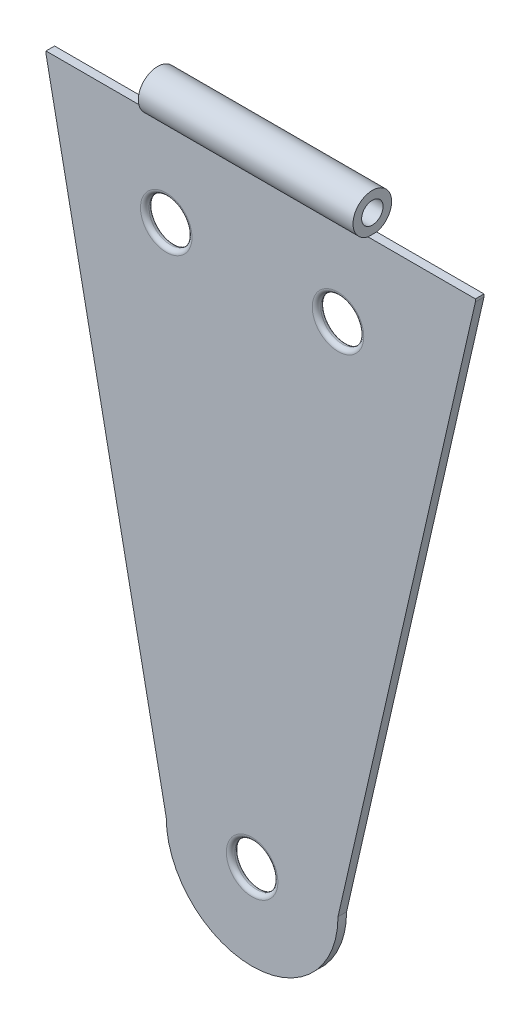
SolidWorks part; units mm, degrees
material "Liga de aço fundido"
ref_plane "Plano frontal" through (0, 0, 0) normal (0, 0, 1) x (1, 0, 0)
ref_plane "Plano superior" through (0, 0, 0) normal (0, 1, 0) x (1, 0, 0)
ref_plane "Plano direito" through (0, 0, 0) normal (1, 0, 0) x (0, 0, -1)
sketch "Esboço1" plane through (0, 0, 0) normal (0, 0, 1) x (1, 0, 0)
  line L5 (-50, 0) -> (50, 0)
  line L6 (-50, 0) -> (-22, 0) construction
  line L17 (-22, 0) -> (-22, -20) construction
  line L31 (-50, 0) -> (-22, -140)
  line L33 (18, -140) -> (50, 0)
  arc A7 (-22, -140) -> (18, -140) centre (-2, -140) ccw
  circle A8 centre (-2, -140) radius 5
  circle A9 centre (-22, -20) radius 5
  circle A10 centre (18, -20) radius 5
  point P5 (0, 0)
  point P10 (0, 0)
  point P12 (0, 0)
  point P13 (0, 0)
  dimension "D3" = 10
  dimension "D6" = 10
  dimension "D1" = 40
  dimension "D2" = 100
  dimension "D4" = 140
  dimension "D5" = 281.31
  dimension "D7" = 20
extrude "Ressalto-extrusão1" add sketch "Esboço1" along normal blind 2 contours A7 L33 L5 L31 | A9 | A10 | A8
fillet "Filete1" radius 1 6 edges at (3, -140, 2) (3, -140, 0) (23, -20, 2) (23, -20, 0) (-17, -20, 2) (-17, -20, 0)
sketch "Esboço6" plane through (0, 0, 0) normal (0, 1, 0) x (1, 0, 0)
  line L4 (50, 0) -> (-50, 0)
  line L5 (-50, 0) -> (-50, -2)
  line L6 (50, 0) -> (-50, 0)
  line L7 (50, -2) -> (50, 0)
  line L9 (-50, 0) -> (-50, -2)
  line L11 (50, -2) -> (50, 0)
  line L12 (-50, -2) -> (50, -2)
  line L13 (-50, -2) -> (50, -2)
  dimension "D1" = 0
extrude "Ressalto-extrusão2" add sketch "Esboço6" along normal blind 5
sketch "Esboço7" plane through (50, 0, 0) normal (1, 0, 0) x (0, 0, -1)
  line L0 (-2, 0) -> (0, 5) construction
  line L4 (-2, 0) -> (0, 0)
  line L5 (0, 0) -> (0, 5)
  line L6 (0, 5) -> (-2, 5)
  line L7 (-2, 5) -> (-2, 0)
  line L8 (-2, 0) -> (0, 0)
  line L9 (0, 0) -> (0, 5)
  line L10 (0, 5) -> (-2, 5)
  line L11 (-2, 5) -> (-2, 0)
  circle A0 centre (-1, 5) radius 2.5
  circle A1 centre (-1, 5) radius 4.5
  dimension "D2" = 5
  dimension "D3" = 2
  dimension "D1" = 0
extrude "Ressalto-extrusão3" add sketch "Esboço7" against normal through all contours L9 A1 L11 A0 region at (50, 8.4189, 3.7274)
sketch "Esboço8" plane through (50, 0, 0) normal (1, 0, 0) x (0, 0, -1)
  arc A0 (0, 2.7087) -> (-2, 2.7087) centre (-1, 5) ccw construction
  arc A1 (0, 2.7087) -> (-2, 2.7087) centre (-1, 5) ccw
  circle A2 centre (-1, 5) radius 2.5
  arc M1 (-2, 2.7087) -> (0, 2.7087) centre (-1, 5) cw
  line M2 (0, 2.7087) -> (0, 5)
  line M3 (0, 5) -> (-2, 5)
  line M4 (-2, 5) -> (-2, 2.7087)
  dimension "D1" = 5
extrude "Corte-extrusão1" cut sketch "Esboço8" against normal through all contours M1 M4 M3 M2 | A2 M4 M2 M3 region at (50, 5.4005, 1) region at (50, 3.7834, 1)
sketch "Esboço9" plane through (0, 0, 0) normal (0, 0, -1) x (-1, 0, 0)
  line L1 (-50, 0.6125) -> (-25, 0.6125)
  line L2 (-50, 0.6125) -> (-50, 25.6125)
  line L3 (-50, 25.6125) -> (-25, 25.6125)
  line L4 (-25, 0.6125) -> (-25, 25.6125)
  line L5 (50, 0.6125) -> (25, 0.6125)
  line L6 (50, 0.6125) -> (50, 25.6125)
  line L7 (50, 25.6125) -> (25, 25.6125)
  line L8 (25, 0.6125) -> (25, 25.6125)
extrude "Corte-extrusão3" cut sketch "Esboço9" against normal through all and the other way through all
